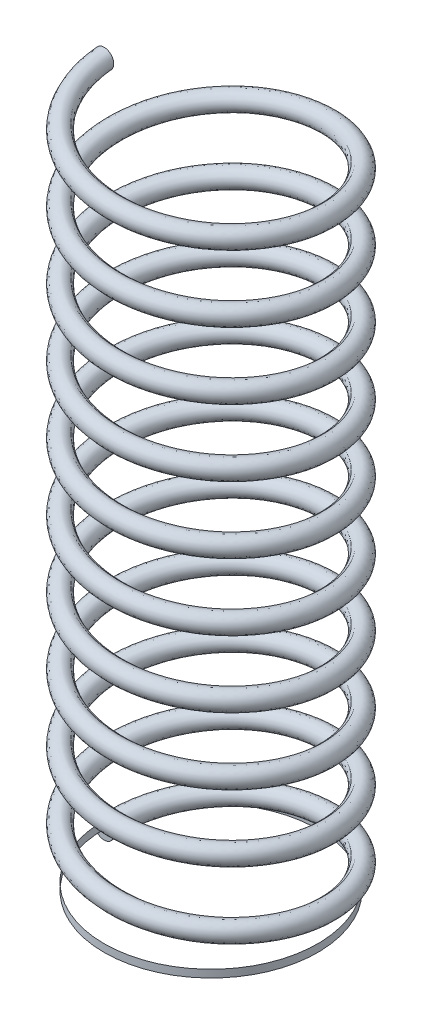
SolidWorks part; units mm, degrees
note: The reader was unsure of these and kept them because the rebuilt part matched: shared geometry of "Sketch1<2>".
ref_plane "Front Plane" through (0, 0, 0) normal (0, 0, 1) x (1, 0, 0)
ref_plane "Top Plane" through (0, 0, 0) normal (0, 1, 0) x (1, 0, 0)
ref_plane "Right Plane" through (0, 0, 0) normal (1, 0, 0) x (0, 0, -1)
sketch "Sketch1" plane through (0, 0, 0) normal (0, 1, 0) x (1, 0, 0)
  circle A0 centre (0, 0) radius 2.8
  dimension "D1" = 5.6
curve "Helix/Spiral1"
sketch "Sketch2" plane through (0, 0, 0) normal (0, 0, 1) x (1, 0, 0)
  circle A0 centre (-2.8, 0) radius 0.25
  dimension "D1" = 0.5
sweep "Sweep1" add profiles "Sketch2" path "Helix/Spiral1"
surface "Surface-Extrude1" sketch "Sketch1<2>" parameters "D1"=0.2
sketch "Sketch1<2>" plane through (0, 0, 0) normal (0, 1, 0) x (1, 0, 0) same geometry as "Sketch1"
equation "\"d\"=5.6"
equation "\"b\"= 0.5"
equation "\"L\"= 17.5"
equation "\"D1@Sketch2\"=\"b\""
equation "\"D1@Sketch1\"=\"d\""
equation "\"D3@Helix/Spiral1\" = \"L\""
